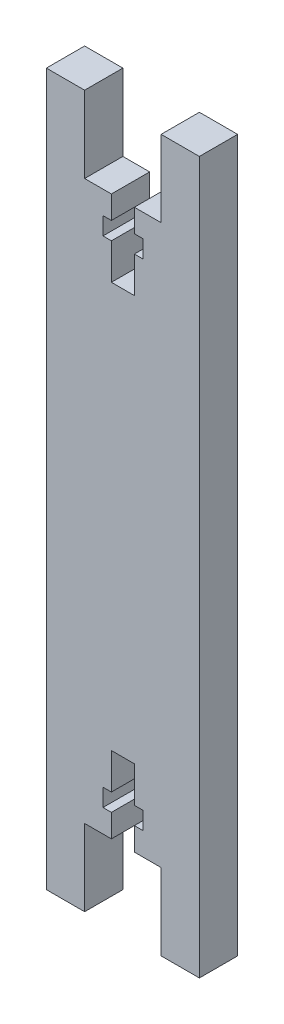
SolidWorks part; units mm, degrees
ref_plane "Front Plane" through (0, 0, 0) normal (0, 0, 1) x (1, 0, 0)
ref_plane "Top Plane" through (0, 0, 0) normal (0, 1, 0) x (1, 0, 0)
ref_plane "Right Plane" through (0, 0, 0) normal (1, 0, 0) x (0, 0, -1)
sketch "Sketch1" plane through (0, 0, 0) normal (0, 0, 1) x (1, 0, 0)
  line L0 (-1.5, 0) -> (-5, 0)
  line L1 (-5, -10) -> (-10, -10)
  line L2 (-10, -10) -> (-10, 0)
  line L3 (-5, -10) -> (-5, 0)
  line L4 (1.5, 0) -> (5, 0)
  line L5 (5, 0) -> (5, -10)
  line L6 (5, -10) -> (10, -10)
  line L7 (10, -10) -> (10, 0)
  line L8 (-1.5, 0) -> (1.5, 0) construction
  line L9 (1.5, 0) -> (1.5, 3)
  line L10 (1.5, 5.3) -> (2.6, 5.3)
  line L11 (-2.6, 3) -> (-2.6, 5.3)
  line L12 (2.6, 3) -> (1.5, 3)
  line L13 (1.5, 5.3) -> (1.5, 10)
  line L14 (1.5, 10) -> (-1.5, 10)
  line L15 (-1.5, 10) -> (-1.5, 5.3)
  line L16 (-1.5, 3) -> (-2.6, 3)
  line L17 (2.6, 5.3) -> (2.6, 3)
  line L18 (-2.6, 5.3) -> (-1.5, 5.3)
  line L19 (-1.5, 3) -> (-1.5, 0)
  line L20 (0, 10) -> (0, 0) construction
  line L21 (-10, 0) -> (-10, 75)
  line L23 (10, 80) -> (10, 0)
  line L24 (0, 70) -> (0, 80) construction
  line L25 (-1.5, 73) -> (1.5, 73) construction
  line L26 (-1.5, 70) -> (-1.5, 73)
  line L27 (-2.6, 67.7) -> (-1.5, 67.7)
  line L28 (2.6, 67.7) -> (2.6, 70)
  line L29 (-1.5, 70) -> (-2.6, 70)
  line L30 (-1.5, 63) -> (-1.5, 67.7)
  line L31 (1.5, 63) -> (-1.5, 63)
  line L32 (1.5, 67.7) -> (1.5, 63)
  line L33 (2.6, 70) -> (1.5, 70)
  line L34 (-2.6, 70) -> (-2.6, 67.7)
  line L35 (1.5, 67.7) -> (2.6, 67.7)
  line L36 (1.5, 73) -> (1.5, 70)
  line L37 (10, 83) -> (10, 80)
  line L39 (5, 73) -> (5, 78)
  line L40 (1.5, 73) -> (5, 73)
  line L41 (-5, 78) -> (-5, 73)
  line L42 (-10, 78) -> (-10, 75)
  line L44 (-1.5, 73) -> (-5, 73)
  line L46 (-10, 78) -> (-10, 83)
  line L55 (-10, 83) -> (-5, 83)
  line L56 (-5, 83) -> (-5, 78)
  line L57 (5, 78) -> (5, 83)
  line L58 (5, 83) -> (10, 83)
  dimension "D1" = 5
  dimension "D2" = 10
  dimension "D3" = 5.2
  dimension "D4" = 3
  dimension "D5" = 2.3
  dimension "D6" = 3
  dimension "D7" = 10
  dimension "D8" = 93
  dimension "D9" = 5
  dimension "D14" = 10
extrude "Boss-Extrude1" add sketch "Sketch1" along normal blind 5
